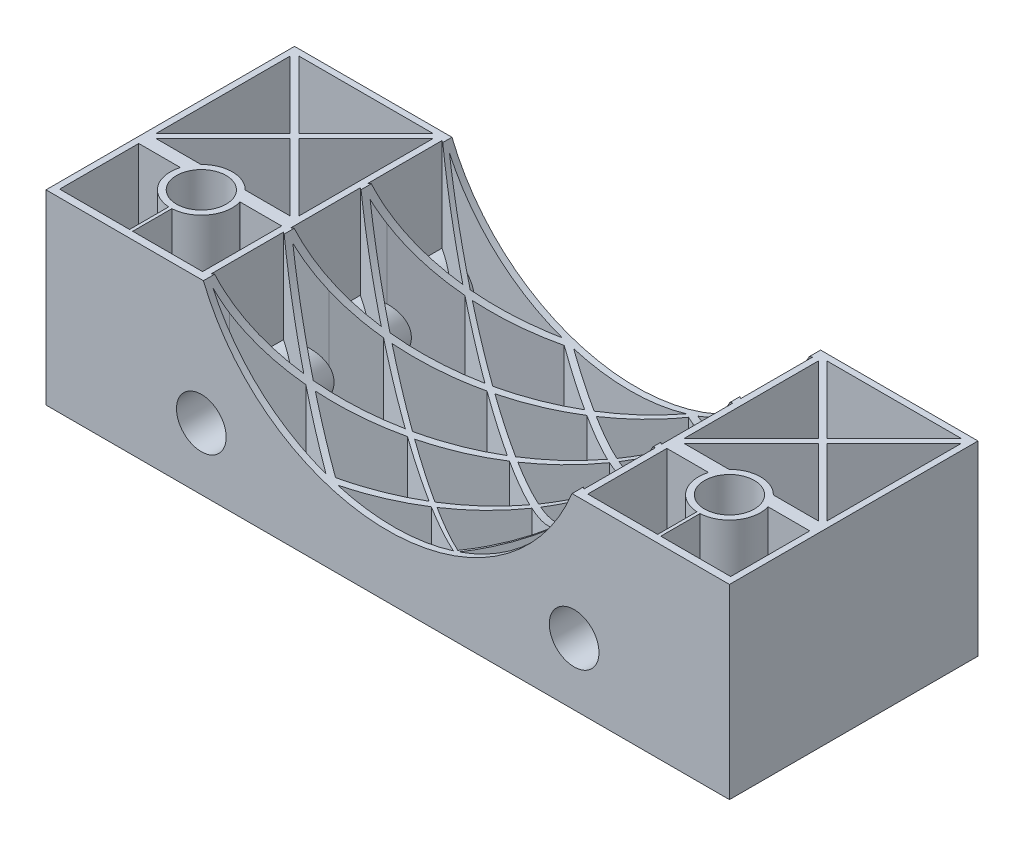
SolidWorks part; units mm, degrees
ref_plane "Front Plane" through (0, 0, 0) normal (0, 0, 1) x (1, 0, 0)
ref_plane "Top Plane" through (0, 0, 0) normal (0, 1, 0) x (1, 0, 0)
ref_plane "Right Plane" through (0, 0, 0) normal (1, 0, 0) x (0, 0, -1)
other "Center of Mass"
ref_plane "Plane1" through (55, 0, 0) normal (1, 0, 0) x (0, 0, -1)
sketch "Sketch1" plane through (0, 0, 0) normal (0, 1, 0) x (1, 0, 0)
  line L1 (0, 0) -> (110, 0)
  line L2 (0, 0) -> (0, 40)
  line L3 (0, 40) -> (110, 40)
  line L4 (110, 0) -> (110, 40)
  dimension "D1" = 110
  dimension "D2" = 40
extrude "Boss-Extrude1" add sketch "Sketch1" along normal blind 30
sketch "Sketch2" plane through (0, 0, 0) normal (0, 0, 1) x (1, 0, 0)
  line L0 (55, 0) -> (55, 10) construction
  line L1 (0, 0) -> (110, 0) construction
  line L2 (55, 10) -> (55, 42) construction
  circle A0 centre (55, 42) radius 32
  point P5 (55, 0)
  dimension "D1" = 10
  dimension "D2" = 32
extrude "Cut-Extrude1" cut sketch "Sketch2" against normal blind 40
sketch "Sketch3" plane through (0, 0, 0) normal (0, -1, 0) x (1, 0, 0)
  line L0 (110, -20) -> (85, -20) construction
  line L2 (110, 0) -> (110, -40) construction
  line L3 (0, -40) -> (0, 0) construction
  line L4 (0, -20) -> (25, -20) construction
  line L5 (0, -12.5) -> (12.5, -12.5) construction
  line L6 (12.5, -12.5) -> (12.5, 0) construction
  line L7 (0, 0) -> (110, 0) construction
  circle A0 centre (12.5, -12.5) radius 4
  dimension "D5" = 8
  dimension "D1" = 25
  dimension "D2" = 25
  dimension "D3" = 12.5
  dimension "D4" = 12.5
extrude "Cut-Extrude3" cut sketch "Sketch3" against normal blind 30
mirror "Mirror1" about plane through (55, 0, 0) normal (1, 0, 0) of "Cut-Extrude3"
sketch "Sketch7" plane through (0, 0, 0) normal (0, 0, 1) x (1, 0, 0)
  line L2 (55, -16.5) -> (55, 16.5) construction
  circle A2 centre (25, 10) radius 4
  circle A4 centre (85, 10) radius 4
  dimension "D1" = 60
extrude "Cut-Extrude6" cut sketch "Sketch7" against normal blind 40
sketch "Sketch9" plane through (0, 0, 0) normal (0, -1, 0) x (1, 0, 0)
  line L0 (12.5, -12.5) -> (12.5, 0) construction
  line L1 (0, 0) -> (110, 0) construction
  line L2 (12.5, 0) -> (12.5, -40) construction
  line L3 (110, -40) -> (0, -40) construction
  line L4 (1.7071, -39) -> (12.5, -28.2071)
  line L5 (25, 0) -> (25, -40) construction
  line L6 (1.7071, -39) -> (21.7913, -39)
  line L7 (0, -40) -> (0, 0) construction
  line L8 (25, -40) -> (0, -15) construction
  line L9 (0, -15) -> (25, -15) construction
  line L10 (25, -15) -> (0, -40) construction
  line L11 (12.5, -28.2071) -> (23.2929, -39)
  line L12 (23.2929, -39) -> (21.7913, -39)
  line L13 (1, -16.7071) -> (11.7929, -27.5)
  line L14 (1, -38.2929) -> (1, -36.7913)
  line L15 (11.7929, -27.5) -> (1, -38.2929)
  line L16 (1, -16.7071) -> (1, -36.7913)
  line L17 (23.2929, -16) -> (12.5, -26.7929)
  line L19 (12.5, -26.7929) -> (1.7071, -16)
  line L21 (24, -38.2929) -> (13.2071, -27.5)
  line L22 (24, -16.7071) -> (24, -18.2087)
  line L23 (13.2071, -27.5) -> (24, -16.7071)
  line L24 (24, -38.2929) -> (24, -18.2087)
  line L26 (1.7071, -16) -> (8.9293, -16)
  line L27 (23.2929, -16) -> (16.3426, -16) [skipped]
  line L28 (1.7071, -16) -> (3.2087, -16) [skipped]
  line L29 (16.0707, -16) -> (23.2929, -16)
  line L31 (12.25, -1.1996) -> (1, -1.1996)
  line L32 (1, -1.1996) -> (1, -13.9249)
  line L33 (12.25, -1.1996) -> (12.25, -7.5063)
  line L34 (1, -13.9249) -> (7.7073, -13.9249)
  line L35 (7.7073, -13.9249) -> (7.6892, -13.8624)
  line L36 (17.2927, -13.9249) -> (17.3108, -13.8624)
  line L37 (12.75, -1.1996) -> (12.75, -7.5063)
  line L38 (24, -13.9249) -> (17.2927, -13.9249)
  line L39 (24, -1.1996) -> (24, -13.9249)
  line L40 (12.75, -1.1996) -> (24, -1.1996)
  line L41 (55, -16.5) -> (55, 16.5) construction
  line L42 (85, -15) -> (110, -40) construction
  line L43 (110, -15) -> (85, -15) construction
  line L44 (85, -40) -> (110, -15) construction
  line L45 (85, 0) -> (85, -40) construction
  line L46 (97.5, 0) -> (97.5, -40) construction
  line L47 (97.5, -12.5) -> (97.5, 0) construction
  line L48 (97.25, -1.1996) -> (86, -1.1996)
  line L49 (86, -1.1996) -> (86, -13.9249)
  line L50 (86, -13.9249) -> (92.7073, -13.9249)
  line L51 (97.25, -1.1996) -> (97.25, -7.5063)
  line L52 (92.7073, -13.9249) -> (92.6892, -13.8624)
  line L53 (102.2927, -13.9249) -> (102.3108, -13.8624)
  line L54 (109, -13.9249) -> (102.2927, -13.9249)
  line L55 (97.75, -1.1996) -> (97.75, -7.5063)
  line L56 (109, -1.1996) -> (109, -13.9249)
  line L57 (97.75, -1.1996) -> (109, -1.1996)
  line L58 (93.9293, -16) -> (86.7071, -16)
  line L59 (108.2929, -16) -> (101.0707, -16)
  line L60 (86, -38.2929) -> (86, -18.2087)
  line L61 (96.7929, -27.5) -> (86, -16.7071)
  line L62 (86, -16.7071) -> (86, -18.2087)
  line L63 (86, -38.2929) -> (96.7929, -27.5)
  line L64 (97.5, -26.7929) -> (108.2929, -16)
  line L65 (86.7071, -16) -> (97.5, -26.7929)
  line L66 (109, -16.7071) -> (109, -36.7913)
  line L67 (98.2071, -27.5) -> (109, -38.2929)
  line L68 (109, -38.2929) -> (109, -36.7913)
  line L69 (109, -16.7071) -> (98.2071, -27.5)
  line L70 (86.7071, -39) -> (88.2087, -39)
  line L71 (97.5, -28.2071) -> (86.7071, -39)
  line L72 (108.2929, -39) -> (88.2087, -39)
  line L73 (108.2929, -39) -> (97.5, -28.2071)
  circle A1 centre (12.5, -12.5) radius 4 construction
  arc A3 (8.9293, -16) -> (16.0707, -16) centre (12.5, -12.5) ccw
  arc A5 (12.25, -7.5063) -> (7.6892, -13.8624) centre (12.5, -12.5) ccw
  arc A6 (12.75, -7.5063) -> (17.3108, -13.8624) centre (12.5, -12.5) cw
  arc A7 (97.25, -7.5063) -> (92.6892, -13.8624) centre (97.5, -12.5) ccw
  arc A8 (97.75, -7.5063) -> (102.3108, -13.8624) centre (97.5, -12.5) cw
  arc A9 (101.0707, -16) -> (93.9293, -16) centre (97.5, -12.5) cw
  point P18 (12.5, -27.5)
  point P36 (12.5, -27.5)
  point P39 (12.5, -16.5)
  point P40 (10.5635, -16)
  point P41 (14.4365, -16)
  point P50 (8.9293, -16)
  point P52 (12.25, -7.5063)
  point P53 (7.7073, -13.9249)
  point P98 (102.2927, -13.9249)
  point P99 (97.75, -7.5063)
  point P100 (101.0707, -16)
  point P101 (95.5635, -16)
  point P102 (99.4365, -16)
  point P103 (97.5, -16.5)
  point P104 (97.5, -27.5)
  dimension "D5" = 0.5
  dimension "D1" = 12.5
  dimension "D2" = 1
  dimension "D3" = 0.5
  dimension "D4" = 4
extrude "Cut-Extrude7" cut sketch "Sketch9" against normal blind 30
sketch "Sketch11" plane through (0, 0, 0) normal (0, -1, 0) x (1, 0, 0)
  line L0 (25, -1) -> (25, -39) construction
  line L1 (25, -39) -> (85, -39) construction
  line L2 (85, -39) -> (85, -1) construction
  line L3 (85, -1) -> (25, -1) construction
  line L4 (0, 0) -> (110, 0) construction
  line L5 (24, -13.9249) -> (24, -1.1996) construction
  line L6 (110, -40) -> (0, -40) construction
  line L7 (86, -16.7071) -> (86, -38.2929) construction
  line L8 (55, -1) -> (55, -39) construction
  line L9 (25, -20) -> (54, -20) construction
  line L10 (85, -1) -> (65, -1)
  line L11 (65, -1) -> (45, -1)
  line L12 (45, -1) -> (25, -1)
  line L13 (25, -1) -> (25, -13.6)
  line L14 (25, -13.6) -> (25, -26.2)
  line L15 (25, -26.2) -> (25, -39)
  line L16 (85, -39) -> (65, -39)
  line L17 (45, -39) -> (25, -39)
  line L18 (85, -39) -> (25, -39) construction
  line L19 (65, -39) -> (45, -39)
  line L20 (25, -13.8) -> (25, -1)
  line L21 (85, -26.2) -> (85, -39)
  line L22 (85, -1) -> (85, -13.6)
  line L23 (85, -13.6) -> (85, -26.2)
  line L24 (25, -13.8) -> (45, -1) construction
  line L25 (25, -26.2) -> (65, -1) construction
  line L26 (25, -39) -> (85, -1) construction
  line L27 (45, -39) -> (85, -13.6) construction
  line L28 (65, -39) -> (85, -26.2) construction
  line L29 (85, -13.6) -> (65, -1) construction
  line L30 (85, -26.2) -> (45, -1) construction
  line L31 (85, -39) -> (25, -1) construction
  line L32 (65, -39) -> (25, -13.8) construction
  line L33 (25.86, -2.1365) -> (81.8164, -37.5756)
  line L34 (25.9456, -2.1907) -> (25, -1.5918)
  line L35 (81.8164, -37.5756) -> (84.0655, -39)
  line L36 (27.2382, -1.8257) -> (83.9174, -37.7225)
  line L37 (27.5296, -2.0103) -> (25.86, -1)
  line L38 (83.9174, -37.7225) -> (85, -38.4082)
  line L39 (28.4232, -12.2028) -> (38.2658, -5.9035)
  line L40 (38.2658, -5.9035) -> (45.9276, -1)
  line L41 (37.2659, -5.3562) -> (44.0724, -1)
  line L42 (37.2659, -5.3562) -> (27.9267, -11.3333)
  line L43 (27.9267, -11.3333) -> (25, -13.2064)
  line L44 (47.7229, -3.3064) -> (79.6333, -23.4099)
  line L45 (79.6333, -23.4099) -> (85, -26.791)
  line L46 (47.7229, -3.3064) -> (44.0724, -1)
  line L47 (45.9276, -1) -> (81.2018, -23.2162)
  line L48 (81.2018, -23.2162) -> (85, -25.6083)
  line L49 (63.0254, -2.5395) -> (28.312, -24.7044)
  line L50 (28.312, -24.7044) -> (25, -26.8191)
  line L51 (28.3301, -23.5111) -> (61.7814, -2.7322)
  line L52 (61.7814, -2.7322) -> (64.5701, -1)
  line L53 (63.0254, -2.5395) -> (65.4364, -1)
  line L54 (65.4364, -1) -> (69.4058, -3.4802)
  line L55 (69.4058, -3.4802) -> (85, -13.2239)
  line L56 (64.5701, -1) -> (67.6965, -2.9943)
  line L57 (67.6965, -2.9943) -> (85, -14.0318)
  line L58 (85, -14.0318) -> (81.3497, -16.5102)
  line L59 (67.4512, -38.0249) -> (82.2284, -28.5675)
  line L60 (82.2284, -28.5675) -> (85, -26.791)
  line L61 (67.4512, -38.0249) -> (65.9299, -39)
  line L62 (65.9299, -39) -> (29.5093, -16.0499)
  line L63 (29.5093, -16.0499) -> (25, -13.2064)
  line L64 (28.0981, -16.3428) -> (62.6323, -38.0993)
  line L65 (62.6323, -38.0993) -> (64.062, -39)
  line L66 (28.0981, -16.3428) -> (25, -14.391)
  line L67 (28.3301, -23.5111) -> (25, -25.5796)
  line L68 (29.5859, -36.6874) -> (82.8637, -2.9448)
  line L69 (82.8637, -2.9448) -> (85, -1.5918)
  line L70 (78.5744, -4.4777) -> (29.2621, -36.0047)
  line L71 (29.2621, -36.0047) -> (25, -38.7297)
  line L72 (29.5859, -36.6874) -> (25.9345, -39)
  line L73 (47.1403, -38.2332) -> (81.3497, -16.5102)
  line L74 (80.4967, -15.8673) -> (46.2437, -37.6179)
  line L75 (46.2437, -37.6179) -> (44.0673, -39)
  line L76 (80.4967, -15.8673) -> (85, -13.0077)
  line L77 (78.5744, -4.4777) -> (84.014, -1)
  line L78 (47.1403, -38.2332) -> (45.9276, -39)
  line L79 (66.8535, -37.2201) -> (80.6496, -28.3906)
  line L80 (80.6496, -28.3906) -> (85, -25.6083)
  line L81 (66.8535, -37.2201) -> (64.062, -39)
  line L82 (28.4232, -12.2028) -> (25, -14.391)
  line L83 (25, -26.2) -> (45, -39) construction
  line L84 (26.8548, -27.9807) -> (42.5394, -38.0189)
  line L85 (42.5394, -38.0189) -> (44.0673, -39)
  line L86 (26.8548, -27.9807) -> (25, -26.8191)
  line L87 (27.6269, -27.2876) -> (43.5979, -37.5091)
  line L88 (43.5979, -37.5091) -> (45.9276, -39)
  line L89 (27.6269, -27.2876) -> (25, -25.5796)
  point P18 (35, 7.2209)
  point P35 (82.8637, -2.9448)
  point P37 (29.5859, -36.6874)
  point P38 (29.2621, -36.0047)
  point P39 (28.312, -24.7044)
  point P40 (28.3301, -23.5111)
  point P41 (28.0981, -16.3428)
  point P42 (29.5093, -16.0499)
  point P43 (28.4232, -12.2028)
  point P44 (27.9267, -11.3333)
  point P45 (37.2659, -5.3562)
  point P46 (38.2658, -5.9035)
  point P47 (49.0942, -2.9884)
  point P48 (47.7229, -3.3064)
  point P49 (81.2018, -23.2162)
  point P50 (79.6333, -23.4099)
  point P51 (80.6496, -28.3906)
  point P52 (82.2284, -28.5675)
  point P53 (80.4967, -15.8673)
  point P54 (81.3497, -16.5102)
  point P55 (81.5522, -11.1324)
  point P56 (81.3412, -11.8859)
  point P57 (69.4058, -3.4802)
  point P58 (67.6965, -2.9943)
  point P59 (61.7814, -2.7322)
  point P60 (63.0254, -2.5395)
  point P84 (47.1403, -38.2332)
  point P86 (46.2437, -37.6179)
  point P87 (62.6323, -38.0993)
  point P88 (67.4512, -38.0249)
  point P100 (78.5744, -4.4777)
  point P110 (66.8535, -37.2201)
  point P116 (27.6269, -27.2876)
  point P117 (26.8548, -27.9807)
  point P118 (42.5394, -38.0189)
  point P119 (43.5979, -37.5091)
  dimension "D1" = 1
  dimension "D2" = 1
  dimension "D3" = 1
  dimension "D4" = 1
  dimension "D5" = 1
  dimension "D6" = 0.5
  dimension "D7" = 0.5
  dimension "D8" = 0.5
  dimension "D9" = 0.5
  dimension "D10" = 0.5
  dimension "D11" = 0.5
  dimension "D12" = 0.5
  dimension "D13" = 0.5
  dimension "D14" = 0.5
  dimension "D15" = 0.5
  dimension "D16" = 0.5
  dimension "D17" = 0.5
  dimension "D18" = 0.5
  dimension "D19" = 0.5
  dimension "D20" = 0.5
  dimension "D21" = 0.5
  dimension "D22" = 0.5
  dimension "D23" = 0.5
  dimension "D24" = 0.5
  dimension "D25" = 0.5
  dimension "D26" = 0.5
  dimension "D27" = 0.5
  dimension "D28" = 0.5
  dimension "D29" = 0.5
  dimension "D30" = 0.5
  dimension "D31" = 0.5
  dimension "D32" = 0.5
  dimension "D33" = 0.5
  dimension "D34" = 0.5
  dimension "D35" = 0.5
  dimension "D36" = 0.5
  dimension "D37" = 0.5
  dimension "D38" = 0.5
  dimension "D39" = 0.5
  dimension "D40" = 0.5
  dimension "D41" = 0.5
  dimension "D42" = 0.5
extrude "Cut-Extrude9" cut sketch "Sketch11" against normal blind 30 contours L42 L41 L12 L37 L36 | L43 L42 L33 L34 L20 | L39 L82 L63 L62 L51 L33 | L36 L51 L44 L46 L40 L39 | L51 L52 L11 L47 | L67 L51 L64 L66 L14 | L89 L87 L70 L64 L49 L50 | L84 L86 L15 L71 L70 | L85 L84 L68 L72 L17 | L87 L88 L75 L74 L64 L68 | L70 L33 L49 L62 | L70 L44 L49 L36 | L70 L57 L56 L53 L49 L47 | L70 L77 L10 L54 L55 | L55 L76 L22 L69 L68 | L74 L76 L57 L68 L47 | L74 L44 L68 L36 | L74 L33 L68 L62 | L81 L79 L33 L73 L62 | L73 L78 L19 L65 L64 | L79 L80 L45 L44 L73 L36 | L73 L47 L48 L23 L58 | L60 L59 L36 L38 L21 | L59 L61 L16 L35 L33 region at (74.7607, 0, -2.9568) region at (81.9172, 0, -7.419) region at (65.0368, 0, -7.1857) region at (55.2273, 0, -2.9434) region at (75.1028, 0, -13.5666) region at (82.0015, 0, -19.8799) region at (45.0868, 0, -7.3656) region at (54.9723, 0, -13.6251) region at (65.0173, 0, -19.9708) region at (35.0131, 0, -2.9234) region at (74.9895, 0, -26.2724) region at (44.9596, 0, -20.0172) region at (81.9597, 0, -32.6107) region at (54.9667, 0, -26.3397) region at (35.0085, 0, -13.7155) region at (28.0405, 0, -7.389) region at (35.0517, 0, -26.3591) region at (64.9645, 0, -32.658) region at (44.9944, 0, -32.6738) region at (27.9809, 0, -19.9985) region at (74.9809, 0, -37.0754) region at (28.111, 0, -32.765) region at (54.9851, 0, -37.089) region at (35.0189, 0, -37.0753)
sketch "Sketch12" plane through (0, 0, 0) normal (0, 0, 1) x (1, 0, 0)
  line L0 (55, -16.5) -> (55, 16.5) construction
  circle A0 centre (25, 10) radius 5
  circle A1 centre (85, 10) radius 5
  point P0 (25, 10)
  dimension "D1" = 10
extrude "Boss-Extrude3" add sketch "Sketch12" against normal blind 40
sketch "Sketch15" plane through (0, 0, 0) normal (0, 0, 1) x (1, 0, 0)
  line L0 (55, -16.5) -> (55, 16.5) construction
  circle A0 centre (25, 10) radius 4
  circle A1 centre (85, 10) radius 4
  point P0 (25, 10)
  dimension "D1" = 8
extrude "Cut-Extrude10" cut sketch "Sketch15" against normal blind 40
